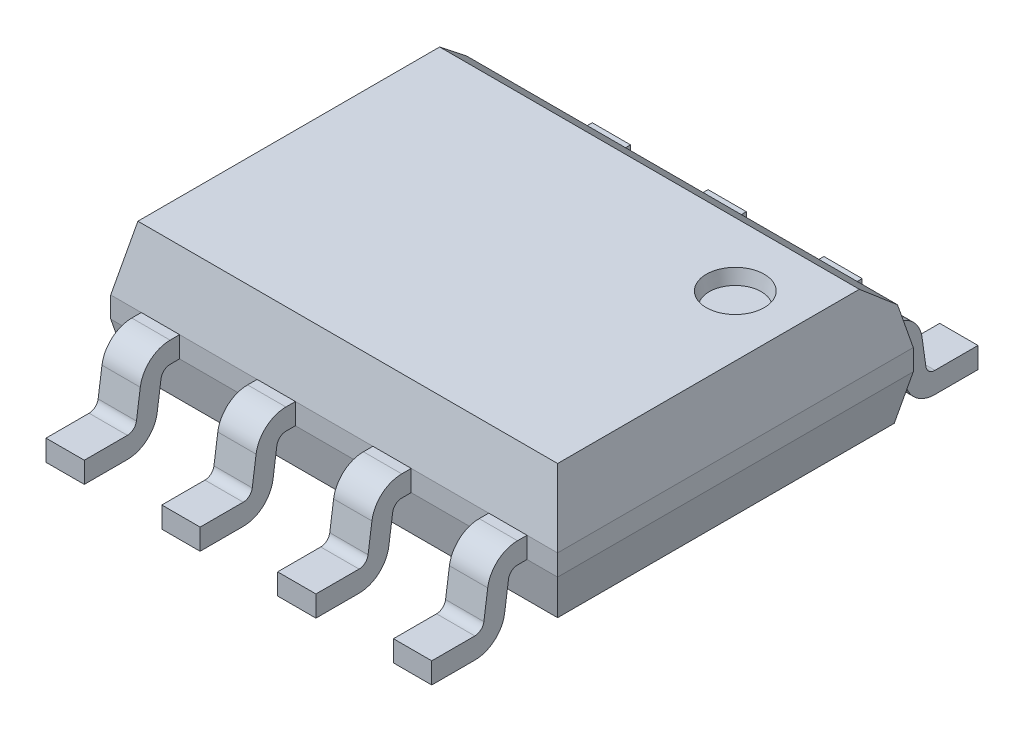
SolidWorks part; units mm, degrees
note: '?' marks a value the reader was unsure of.
ref_plane "Front Plane" through (0, 0, 0) normal (0, 0, 1) x (1, 0, 0)
ref_plane "Top Plane" through (0, 0, 0) normal (0, 1, 0) x (1, 0, 0)
ref_plane "Right Plane" through (0, 0, 0) normal (1, 0, 0) x (0, 0, -1)
ref_axis "Axis1" through (2.06, 0, 0) along (-1, 0, 0)?
sketch "Sketch1" plane through (0, 0, 0) normal (0, 1, 0) x (1, 0, 0)
  line L1 (-3.085, 1.95) -> (1.815, 1.95)
  line L2 (-3.085, 1.95) -> (-3.085, -1.95)
  line L3 (-3.085, -1.95) -> (1.815, -1.95)
  line L4 (1.815, 1.95) -> (1.815, -1.95)
  dimension "D1" = 4.9
  dimension "D2" = 3.9
  dimension "D3" = 3.085
  dimension "D4" = 1.95
extrude "Extrude1" add sketch "Sketch1" along normal blind 0.7 draft 12 and the other way blind 0.23
sketch "Sketch2" plane through (0, -0.23, 0) normal (0, -1, 0) x (1, 0, 0)
  line L4 (-3.085, 1.95) -> (-3.085, -1.95)
  line L5 (-3.085, -1.95) -> (1.815, -1.95)
  line L6 (1.815, -1.95) -> (1.815, 1.95)
  line L7 (1.815, 1.95) -> (-3.085, 1.95)
  line L8 (-3.085, 1.95) -> (-3.085, -1.95)
  line L9 (-3.085, -1.95) -> (1.815, -1.95)
  line L10 (1.815, -1.95) -> (1.815, 1.95)
  line L11 (1.815, 1.95) -> (-3.085, 1.95)
  dimension "D1" = 0
extrude "Extrude2" add sketch "Sketch2" along normal blind 0.49 draft 12
chamfer "Chamfer1" distance 0.3 angle 38.5 1 edges at (-0.635, 0.7, -1.8012)
sketch "Sketch3" plane through (0, 0.7, 0) normal (0, 1, 0) x (-1, 0, 0)
  circle A0 centre (-1.0015, -0.8119) radius 0.3175
extrude "Cut-Extrude1" cut sketch "Sketch3" against normal blind 0.15 draft 12
sketch "Sketch4" plane through (0, 0, 0) normal (1, 0, 0) x (0, 0, -1)
  line L0 (1.95, -0.23) -> (-1.95, -0.23) construction
  line L1 (1.95, 0) -> (-1.95, 0) construction
  line L2 (1.95, -0.23) -> (-1.95, -0.23)
  line L3 (1.95, 0) -> (-1.95, 0)
  line L4 (-1.8458, -0.72) -> (1.8458, -0.72) construction
  line L5 (2.995, -0.67) -> (2.4354, -0.67)
  line L6 (2.995, -0.67) -> (2.995, -0.9)
  line L7 (2.995, -0.9) -> (2.2355, -0.9)
  line L8 (2.155, -0.67) -> (2.155, -0.9) construction
  line L9 (-2.155, -0.67) -> (-2.4354, -0.67) construction
  line L10 (-2.155, -0.67) -> (-2.155, -0.9) construction
  line L11 (-2.155, -0.9) -> (-2.2355, -0.9) construction
  line L12 (-2.995, -0.67) -> (-2.995, -0.9)
  line L13 (1.95, 0) -> (2.3413, 0)
  line L14 (2.6703, 0) -> (2.6703, -0.23) construction
  line L15 (2.6703, -0.23) -> (2.1413, -0.23) construction
  line L16 (-1.95, 0) -> (-2.3413, 0)
  line L17 (-2.6934, 0) -> (-2.6934, -0.23) construction
  line L18 (-2.6934, -0.23) -> (-2.1413, -0.23) construction
  line L19 (2.3413, 0) -> (2.6703, 0) construction
  line L20 (2.4354, -0.67) -> (2.3413, 0)
  line L21 (2.2355, -0.9) -> (2.1413, -0.23)
  line L22 (2.1413, -0.23) -> (1.95, -0.23)
  line L23 (2.2355, -0.9) -> (2.155, -0.9) construction
  line L24 (2.4354, -0.67) -> (2.155, -0.67) construction
  line L25 (0, -1.1578) -> (0, -1.9582) construction
  line L26 (-2.2355, -0.9) -> (-2.1413, -0.23)
  line L27 (-2.4354, -0.67) -> (-2.3413, 0)
  line L28 (-2.1413, -0.23) -> (-1.95, -0.23)
  line L29 (-2.3413, 0) -> (-2.6934, 0) construction
  line L30 (-2.4354, -0.67) -> (-2.995, -0.67)
  line L31 (-2.2355, -0.9) -> (-2.995, -0.9)
  dimension "D1" = 0.84
  dimension "D2" = 5.99
  dimension "D3" = 2.995
  dimension "D4" = 0.18
  dimension "D5" = 0.23
  dimension "D6" = 0.23
extrude "Extrude3" add sketch "Sketch4" along normal blind 0.21 and the other way blind 0.21
pattern_linear "LPattern3" count 2 spacing 1.27 along (1, 0, 0) count 3 spacing 1.27 along (-1, 0, 0) of "Extrude3"
fillet "Fillet1" radius 0.1 16 edges at (0, -0.67, 2.4354) (0, -0.23, 2.1413) (0, -0.67, -2.4354) (0, -0.23, -2.1413) (-2.54, -0.67, 2.4354) (-1.27, -0.67, 2.4354) (1.27, -0.67, 2.4354) (1.27, -0.67, -2.4354) (-1.27, -0.67, -2.4354) (-2.54, -0.67, -2.4354) (-2.54, -0.23, 2.1413) (-1.27, -0.23, 2.1413) (1.27, -0.23, 2.1413) (-2.54, -0.23, -2.1413) (-1.27, -0.23, -2.1413) (1.27, -0.23, -2.1413)
fillet "Fillet2" radius 0.33 16 edges at (0, 0, 2.3413) (0, -0.9, 2.2355) (0, -0.9, -2.2355) (0, 0, -2.3413) (-2.54, -0.9, -2.2355) (-1.27, -0.9, -2.2355) (1.27, -0.9, -2.2355) (1.27, -0.9, 2.2355) (-1.27, -0.9, 2.2355) (-2.54, -0.9, 2.2355) (1.27, 0, 2.3413) (-1.27, 0, 2.3413) (-2.54, 0, 2.3413) (-2.54, 0, -2.3413) (-1.27, 0, -2.3413) (1.27, 0, -2.3413)
ref_plane "Plane1" through (0, -0.9, 0) normal (0, 1, 0) x (-1, 0, 0)
sketch "Component_Outline" plane through (0, -0.9, 0) normal (0, 1, 0) x (-1, 0, 0)
  line L0 (2.75, 2.995) -> (2.75, 1.95)
  line L1 (0.21, -2.995) -> (-0.21, -2.995)
  line L2 (2.33, -2.995) -> (2.33, -1.95)
  line L3 (2.33, -1.95) -> (1.48, -1.95)
  line L4 (1.48, -2.995) -> (1.48, -1.95)
  line L5 (-1.06, -2.995) -> (-1.48, -2.995)
  line L6 (1.06, -2.995) -> (1.06, -1.95)
  line L7 (1.06, -1.95) -> (0.21, -1.95)
  line L8 (0.21, -2.995) -> (0.21, -1.95)
  line L9 (-0.21, 2.995) -> (0.21, 2.995)
  line L10 (-0.21, -2.995) -> (-0.21, -1.95)
  line L11 (-0.21, -1.95) -> (-1.06, -1.95)
  line L12 (-1.06, -2.995) -> (-1.06, -1.95)
  line L13 (2.33, 1.95) -> (1.48, 1.95)
  line L14 (2.33, 1.95) -> (2.33, 2.995)
  line L16 (1.48, 1.95) -> (1.48, 2.995)
  line L17 (1.06, 1.95) -> (0.21, 1.95)
  line L18 (1.06, 1.95) -> (1.06, 2.995)
  line L19 (2.33, 2.995) -> (2.75, 2.995)
  line L20 (0.21, 1.95) -> (0.21, 2.995)
  line L21 (-0.21, 1.95) -> (-1.06, 1.95)
  line L22 (-0.21, 1.95) -> (-0.21, 2.995)
  line L23 (1.06, 2.995) -> (1.48, 2.995)
  line L24 (-1.06, 1.95) -> (-1.06, 2.995)
  line L25 (2.75, 1.95) -> (3.085, 1.95)
  line L26 (3.085, 1.95) -> (3.085, -1.95)
  line L27 (3.085, -1.95) -> (2.75, -1.95)
  line L28 (2.75, -1.95) -> (2.75, -2.995)
  line L29 (2.75, -2.995) -> (2.33, -2.995)
  line L30 (-1.48, -2.995) -> (-1.48, -1.95)
  line L31 (-1.48, -1.95) -> (-1.815, -1.95)
  line L32 (-1.815, -1.95) -> (-1.815, 1.95)
  line L33 (-1.815, 1.95) -> (-1.48, 1.95)
  line L34 (-1.48, 1.95) -> (-1.48, 2.995)
  line L35 (-1.48, 2.995) -> (-1.06, 2.995)
  line L36 (1.48, -2.995) -> (1.06, -2.995)
